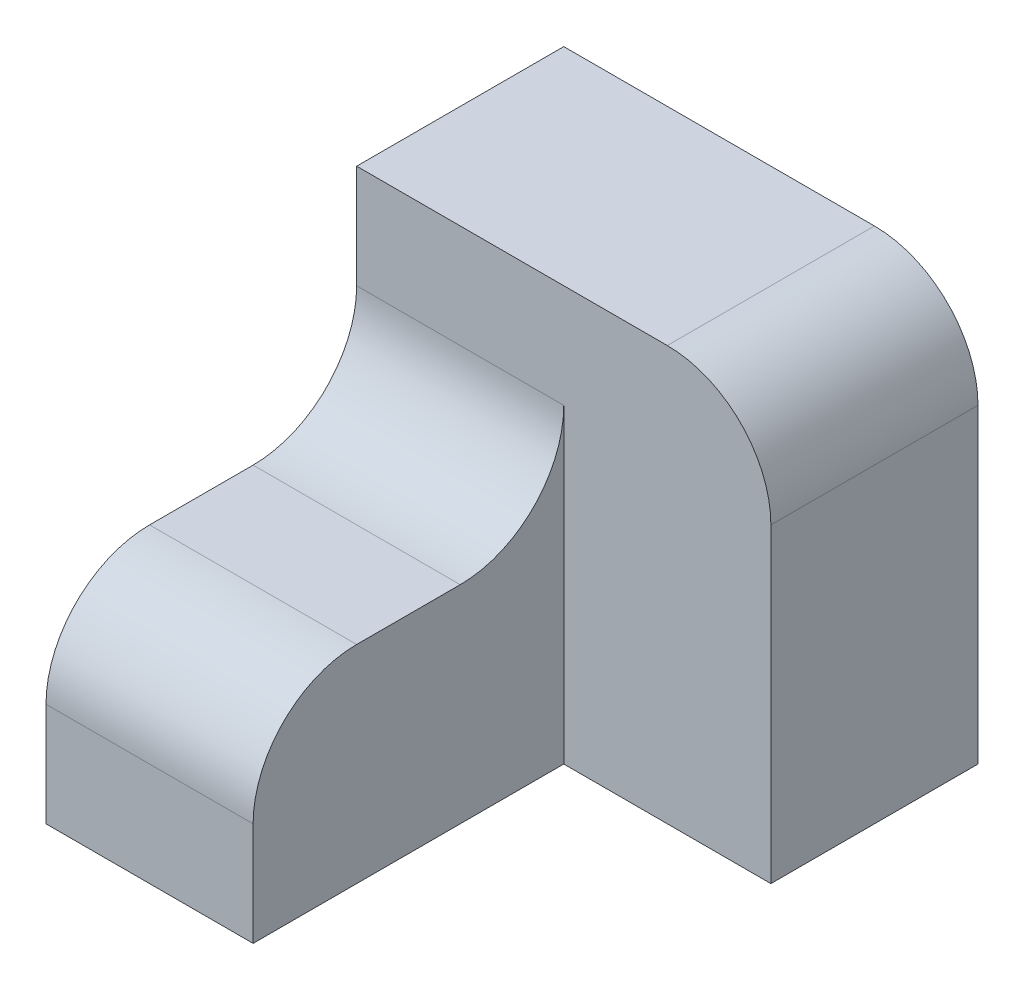
SolidWorks part; units mm, degrees
ref_plane "前基準面" through (0, 0, 0) normal (0, 0, 1) x (1, 0, 0)
ref_plane "上基準面" through (0, 0, 0) normal (0, 1, 0) x (1, 0, 0)
ref_plane "右基準面" through (0, 0, 0) normal (1, 0, 0) x (0, 0, -1)
sketch "Sketch1" plane through (0, 0, 0) normal (0, 1, 0) x (1, 0, 0)
  line L0 (0, 0) -> (20, 0)
  line L1 (20, 0) -> (20, 30)
  line L2 (20, 30) -> (40, 30)
  line L3 (40, 30) -> (40, 50)
  line L4 (40, 50) -> (0, 50)
  line L5 (0, 50) -> (0, 0)
  line L6 (20, 30) -> (0, 30)
  dimension "D1" = 20
  dimension "D2" = 30
  dimension "D3" = 20
  dimension "D4" = 20
extrude "填料-伸長1" add sketch "Sketch1" along normal blind 20 contours L1 L6 L5 L0 region at (10, 0, -15)
extrude "填料-伸長2" add sketch "草圖1<3>" along normal blind 40 contours L6 L2 L3 L4 L5 region at (20, 0, -40)
sketch "草圖1<3>" plane through (0, 0, 0) normal (0, 1, 0) x (1, 0, 0) same geometry as "Sketch1"
fillet "圓角1" radius 10 3 edges at (40, 40, -40) (10, 20, 0) (10, 20, -30)
